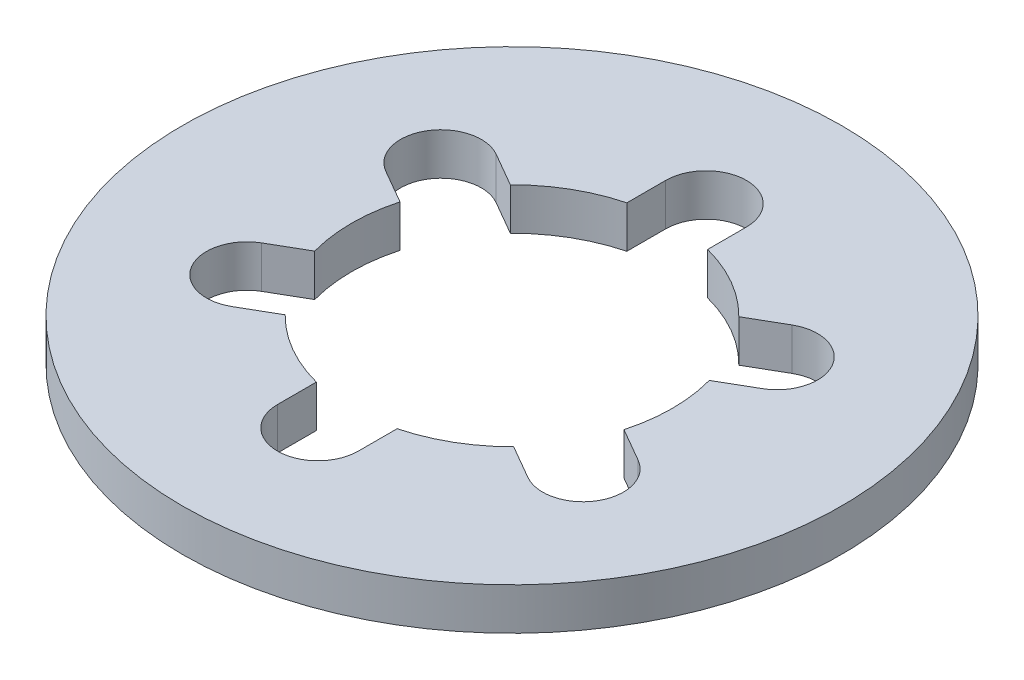
SolidWorks part; units mm, degrees
ref_plane "Front Plane" through (0, 0, 0) normal (0, 0, 1) x (1, 0, 0)
ref_plane "Top Plane" through (0, 0, 0) normal (0, 1, 0) x (1, 0, 0)
ref_plane "Right Plane" through (0, 0, 0) normal (1, 0, 0) x (0, 0, -1)
sketch "Sketch1" plane through (0, 0, 0) normal (0, 1, 0) x (1, 0, 0)
  circle A0 centre (0, 0) radius 2.825
  circle A1 centre (0, 0) radius 1.375
  dimension "D1" = 5.65
  dimension "D2" = 2.75
extrude "Boss-Extrude1" add sketch "Sketch1" along normal blind 0.36
sketch "Sketch2" plane through (0, 0.36, 0) normal (0, 1, 0) x (1, 0, 0)
  line L0 (0, -1.6638) -> (0, 1.6638) construction
  line L1 (-0.3462, -1.6638) -> (-0.3462, 1.6638)
  line L2 (0.3462, -1.6638) -> (0.3462, 1.6638)
  arc A0 (-0.3462, -1.6638) -> (0.3462, -1.6638) centre (0, -1.6638) ccw
  arc A1 (0.3462, 1.6638) -> (-0.3462, 1.6638) centre (0, 1.6638) ccw
  point P2 (0, 0)
extrude "Cut-Extrude1" cut sketch "Sketch2" against normal through all
ref_axis "Axis1" through (0, 0.36, 0) along (0, -1, 0)
pattern_circular "CirPattern1" count 3 every 60 about axis through (0, 0.36, 0) along (0, -1, 0) of "Cut-Extrude1"
